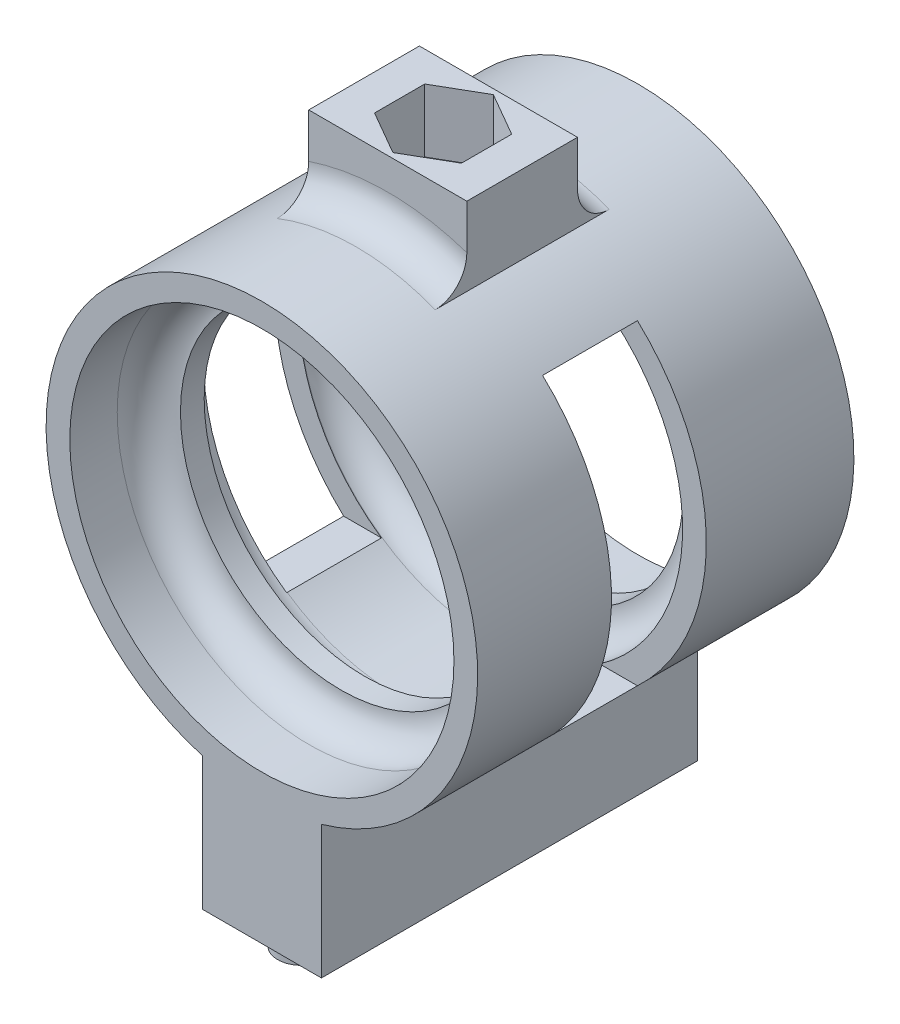
SolidWorks part; units mm, degrees
ref_plane "Front Plane" through (0, 0, 0) normal (0, 0, 1) x (1, 0, 0)
ref_plane "Top Plane" through (0, 0, 0) normal (0, 1, 0) x (1, 0, 0)
ref_plane "Right Plane" through (0, 0, 0) normal (1, 0, 0) x (0, 0, -1)
sketch "Sketch1" plane through (0, 0, 0) normal (0, 0, 1) x (1, 0, 0)
  line L0 (-3.7667, -13.12) -> (3.7667, -13.12)
  line L1 (0, -55) -> (0, 55) construction
  line L2 (0, -13.65) -> (6.7961, -13.65) construction
  circle A0 centre (0, 0) radius 12.15
  circle A1 centre (0, 0) radius 13.65
  point P6 (0, -13.12)
  dimension "D1" = 24.3
  dimension "D2" = 27.3
  dimension "D3" = 0.53
extrude "Boss-Extrude1" add sketch "Sketch1" along normal blind 23.8 contours L0 A1 A0 region at (-7.983, 10.5973, 0)
sketch "Sketch2" plane through (0, 0, 23.8) normal (0, 0, 1) x (1, 0, 0)
  circle A1 centre (0, 0) radius 12.15
  circle A2 centre (0, 0) radius 10.15
  circle A3 centre (0, 0) radius 10.15
  dimension "D1" = 2
extrude "Boss-Extrude2" add sketch "Sketch2" against normal blind 1.5 from offset 5 offset against normal yes
extrude "Boss-Extrude3" add sketch "Sketch2<2>" along normal blind 1.5 from offset 18 offset against normal yes
sketch "Sketch2<2>" plane through (0, 0, 23.8) normal (0, 0, 1) x (1, 0, 0) same geometry as "Sketch2"
sketch "Sketch4" plane through (0, 0, 0) normal (1, 0, 0) x (0, 0, -1)
  line L0 (13.09, 0) -> (-13.09, 0) construction
  line L1 (-15.3358, -10) -> (-9.3358, -10)
  line L2 (-15.3358, -10) -> (-15.3358, 10)
  line L3 (-15.3358, 10) -> (-9.3358, 10)
  line L4 (-9.3358, -10) -> (-9.3358, 10)
  line L5 (-15.3358, -10) -> (-9.3358, 10) construction
  line L6 (-15.3358, 10) -> (-9.3358, -10) construction
  point P0 (-12.3358, 0)
  dimension "D1" = 20
  dimension "D2" = 6
extrude "Cut-Extrude1" cut sketch "Sketch4" against normal through all both and the other way through all
sketch "Sketch5" plane through (0, -13.12, 0) normal (0, -1, 0) x (1, 0, 0)
  line L0 (0, 23.8) -> (0, 0) construction
  line L1 (-3.7667, 23.8) -> (3.7667, 23.8) construction
  line L2 (0, 21.3) -> (0, 2.5) construction
  circle A0 centre (0, 21.3) radius 1.5
  circle A1 centre (0, 2.5) radius 1.5
  point P7 (0, 11.9)
  point P8 (0, 11.9)
  dimension "D2" = 3
  dimension "D3" = 3
  dimension "D1" = 18.8
extrude "Boss-Extrude4" add sketch "Sketch5" along normal blind 9.8
fillet "Fillet1" radius 2 4 edges at (12.15, 0, 5.8) (12.15, 0, 7.3) (12.15, 0, 17.3) (12.15, 0, 18.8)
sketch "Sketch7" plane through (0, -13.12, 0) normal (0, -1, 0) x (1, 0, 0)
  line L0 (15.015, 0) -> (-15.015, 0) construction
  line L1 (-3.7667, 23.8) -> (3.7667, 23.8)
  line L2 (-3.7667, 23.8) -> (-3.7667, 0)
  line L3 (-3.7667, 0) -> (3.7667, 0)
  line L4 (3.7667, 23.8) -> (3.7667, 0)
  line L5 (3.7667, 23.8) -> (3.7667, 0) construction
extrude "Boss-Extrude5" add sketch "Sketch7" along normal blind 8.42
ref_plane "Plane2" through (0, 0, 15.3358) normal (0, 0, -1) x (-1, 0, 0)
sketch "Sketch8" plane through (0, 0, 15.3358) normal (0, 0, -1) x (-1, 0, 0)
  line L0 (0, 13.65) -> (-5, 13.65)
  line L1 (-5, 13.65) -> (-5, 12.7013)
  line L2 (0, 13.65) -> (5, 13.65)
  line L3 (5, 13.65) -> (5, 12.7013)
  line L4 (0, 13.09) -> (0, -13.09) construction
  arc A0 (3.7667, -13.12) -> (-3.7667, -13.12) centre (0, 0) ccw construction
  arc A1 (-5, 12.7013) -> (5, 12.7013) centre (0, 0) cw
  point P9 (9.291, 10)
  point P13 (0, 0)
  dimension "D1" = 5
extrude "Boss-Extrude7" add sketch "Sketch8" along normal blind 6.5 and the other way blind 0.5 contours L1 A1 L0 | L2 A1 L3 region at (3.7589, 13.3672, 15.3358) region at (-3.7589, 13.3672, 15.3358)
sketch "Sketch9" plane through (0, 13.65, 0) normal (0, 1, 0) x (1, 0, 0)
  line L0 (0, -13.09) -> (0, 13.09) construction
  line L1 (0, -8.8358) -> (0, -15.8358) construction
  line L2 (0, -8.8358) -> (5, -8.8358) construction
  line L3 (0, -15.8358) -> (5, -15.8358) construction
  line L5 (0, -15.5112) -> (2.75, -13.9235)
  line L6 (2.75, -13.9235) -> (2.75, -10.748)
  line L7 (2.75, -10.748) -> (0, -9.1603)
  line L8 (0, -9.1603) -> (-2.75, -10.748)
  line L9 (-2.75, -10.748) -> (-2.75, -13.9235)
  line L10 (-2.75, -13.9235) -> (0, -15.5112)
  line L11 (-5, -8.8358) -> (5, -8.8358)
  line L12 (-5, -8.8358) -> (-5, -15.8358)
  line L13 (-5, -15.8358) -> (5, -15.8358)
  line L14 (5, -8.8358) -> (5, -15.8358)
  circle A0 centre (0, -12.3358) radius 1.6
  circle A1 centre (0, -12.3358) radius 2.75 construction
  point P10 (0, -12.3358)
  point P24 (0, -9.1603)
  line M8 (0, -15.8358) -> (5, -15.8358)
  line M9 (5, -15.8358) -> (5, -8.8358)
  line M10 (5, -8.8358) -> (0, -8.8358)
  line M11 (0, -8.8358) -> (-5, -8.8358)
  line M12 (-5, -8.8358) -> (-5, -15.8358)
  line M13 (-5, -15.8358) -> (0, -15.8358)
  dimension "D1" = 3.2
  dimension "D2" = 5.5
extrude "Cut-Extrude2" cut sketch "Sketch9" against normal up to next contours A0 region at (0, 13.65, 12.3358)
extrude "Boss-Extrude8" add sketch "Sketch9<3>" along normal blind 4 contours L10 L9 L8 L7 L6 L5 M13 M8 M9 M10 M11 M12 region at (-2.5, 13.65, 8.9578)
sketch "Sketch9<3>" plane through (0, 13.65, 0) normal (0, 1, 0) x (1, 0, 0) same geometry as "Sketch9"
fillet "Fillet2" radius 2 2 edges at (0, 13.65, 15.8358) (0, 13.65, 8.8358)
